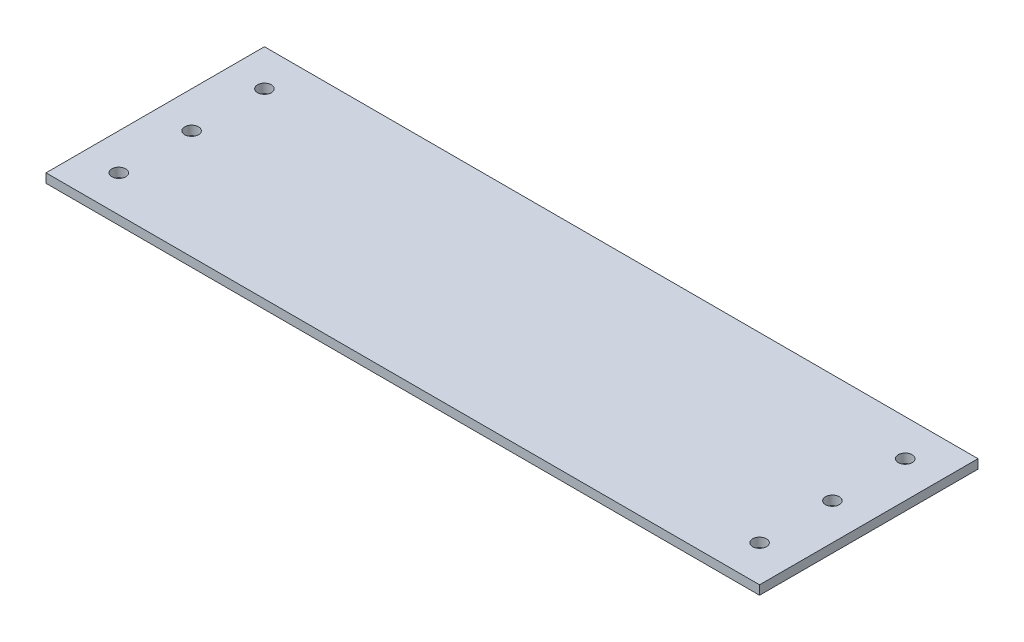
SolidWorks part; units mm, degrees
material "6061 Alloy"
ref_plane "Front Plane" through (0, 0, 0) normal (0, 0, 1) x (1, 0, 0)
ref_plane "Top Plane" through (0, 0, 0) normal (0, 1, 0) x (1, 0, 0)
ref_plane "Right Plane" through (0, 0, 0) normal (1, 0, 0) x (0, 0, -1)
sketch "Sketch1" plane through (0, 0, 0) normal (0, 1, 0) x (1, 0, 0)
  line L0 (0, 38.1) -> (248.92, 38.1) construction
  line L1 (0, 0) -> (248.92, 0)
  line L2 (0, 0) -> (0, 76.2)
  line L3 (0, 76.2) -> (248.92, 76.2)
  line L4 (248.92, 0) -> (248.92, 76.2)
  line L5 (0, 63.5) -> (12.7, 63.5) construction
  line L6 (12.7, 63.5) -> (12.7, 12.7) construction
  line L7 (124.46, 76.2) -> (124.46, 0) construction
  line L8 (12.7, 63.5) -> (236.22, 63.5) construction
  circle A0 centre (12.7, 63.5) radius 2.413
  circle A1 centre (12.7, 38.1) radius 2.413
  circle A2 centre (12.7, 12.7) radius 2.413
  circle A3 centre (236.22, 12.7) radius 2.413
  circle A4 centre (236.22, 38.1) radius 2.413
  circle A5 centre (236.22, 63.5) radius 2.413
  dimension "D3" = 4.826
  dimension "D6" = 12.7
  dimension "D1" = 223.52
  dimension "D2" = 76.2
  dimension "D5" = 12.7
  dimension "D4" = 3
extrude "Boss-Extrude1" add sketch "Sketch1" along normal blind 3.175
